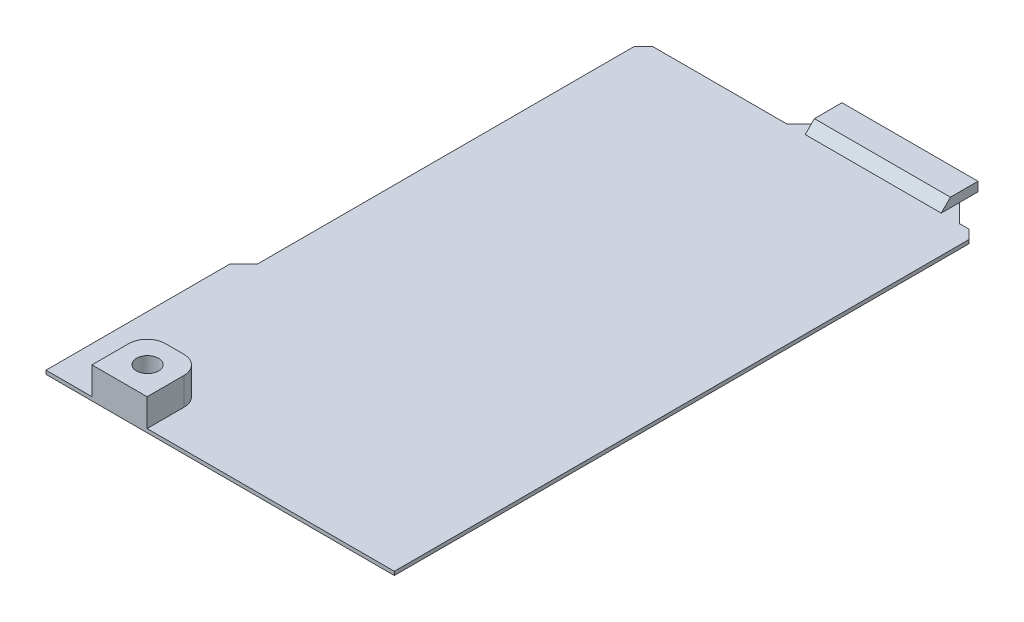
SolidWorks part; units mm, degrees
ref_plane "前视基准面" through (0, 0, 0) normal (0, 0, 1) x (1, 0, 0)
ref_plane "上视基准面" through (0, 0, 0) normal (0, 1, 0) x (1, 0, 0)
ref_plane "右视基准面" through (0, 0, 0) normal (1, 0, 0) x (0, 0, -1)
sketch "草图1" plane through (0, 0, 0) normal (0, 1, 0) x (1, 0, 0)
  line L0 (38, 63.5) -> (38, 0) construction
  line L1 (0, 0) -> (37.9, 0)
  line L2 (0, 0) -> (0, 20)
  line L3 (2.5, 63.5) -> (17.1, 63.5)
  line L4 (37.9, 0) -> (37.9, 62.5)
  line L5 (1.4, 63.5) -> (17, 63.5) construction
  line L7 (1.5, 62.5) -> (1.5, 21.5)
  line L8 (30, 50) -> (0, 20) construction
  line L9 (1.5, 21.5) -> (0, 20)
  line L10 (1.4, 32.6) -> (1.4, 64.1) construction
  line L11 (36.9, 63.5) -> (37.9, 62.5)
  line L12 (1.5, 62.5) -> (2.5, 63.5)
  line L16 (33.9, 65.5) -> (19.1, 65.5)
  line L19 (34, 65.5) -> (19, 65.5) construction
  line L20 (35.9, 63.5) -> (36.9, 63.5)
  line L21 (35.9, 63.5) -> (33.9, 65.5)
  line L22 (17.1, 63.5) -> (19.1, 65.5)
  line L27 (34, 67.9) -> (34, 62.5) construction
  line L28 (19, 62.5) -> (19, 67.9) construction
  point P1 (37.9, 63.5)
  point P9 (1.5, 63.5)
  point P18 (33.9, 63.5)
  dimension "D3" = 0.1
  dimension "D1" = 0.1
  dimension "D2" = 0
  dimension "D4" = 2
  dimension "D5" = 0.1
  dimension "D8" = 0
  dimension "D9" = 0.1
extrude "凸台-拉伸1" add sketch "草图1" along normal blind 1
chamfer "倒角1" distance 0.6 angle 45 12 edges at (18.95, 0, 0) (37.9, 0, -31.25) (37.4, 0, -63) (36.4, 0, -63.5) (34.9, 0, -64.5) (26.5, 0, -65.5) (18.1, 0, -64.5) (9.8, 0, -63.5) (2, 0, -63) (1.5, 0, -42) (0.75, 0, -20.75) (0, 0, -10)
sketch "草图2" plane through (0, 1, 0) normal (0, 1, 0) x (1, 0, 0)
  line L0 (33.9, 65.5) -> (19.1, 65.5) construction
  line L1 (19.1, 67.5) -> (33.9, 67.5)
  line L2 (19.1, 67.5) -> (19.1, 63.5)
  line L3 (19.1, 63.5) -> (33.9, 63.5)
  line L4 (33.9, 67.5) -> (33.9, 63.5)
  dimension "D1" = 2
  dimension "D2" = 2
extrude "凸台-拉伸2" add sketch "草图2" along normal blind 1
sketch "草图3" plane through (0, 1, 0) normal (0, 1, 0) x (1, 0, 0)
  line L4 (5, 4) -> (5, 0)
  line L5 (9, 6) -> (7, 6)
  line L6 (11, 0) -> (11, 4)
  line L7 (5, 0) -> (11, 0)
  line L8 (5, 4) -> (5, 0)
  line L9 (9, 6) -> (7, 6)
  line L10 (11, 0) -> (11, 4)
  line L11 (5, 0) -> (11, 0)
  arc A2 (7, 6) -> (5, 4) centre (7, 4) ccw
  arc A3 (11, 4) -> (9, 6) centre (9, 4) ccw
  arc A4 (7, 6) -> (5, 4) centre (7, 4) ccw
  arc A5 (11, 4) -> (9, 6) centre (9, 4) ccw
  dimension "D1" = 0
extrude "凸台-拉伸3" add sketch "草图3" along normal blind 3
sketch "草图4" plane through (0, 0, 0) normal (0, -1, 0) x (1, 0, 0)
  circle A0 centre (8, -3.05) radius 1.2 construction
  circle A1 centre (8, -3.05) radius 1.2
extrude "切除-拉伸1" cut sketch "草图4" against normal through all
sketch "草图5" plane through (0, 0, 0) normal (0, -1, 0) x (1, 0, 0)
  circle A0 centre (8, -3.05) radius 2.05 construction
  circle A1 centre (8, -3.05) radius 2.05
extrude "切除-拉伸2" cut sketch "草图5" against normal blind 2
chamfer "倒角2" distance 1 angle 45 1 edges at (26.5, 2, -63.5)
